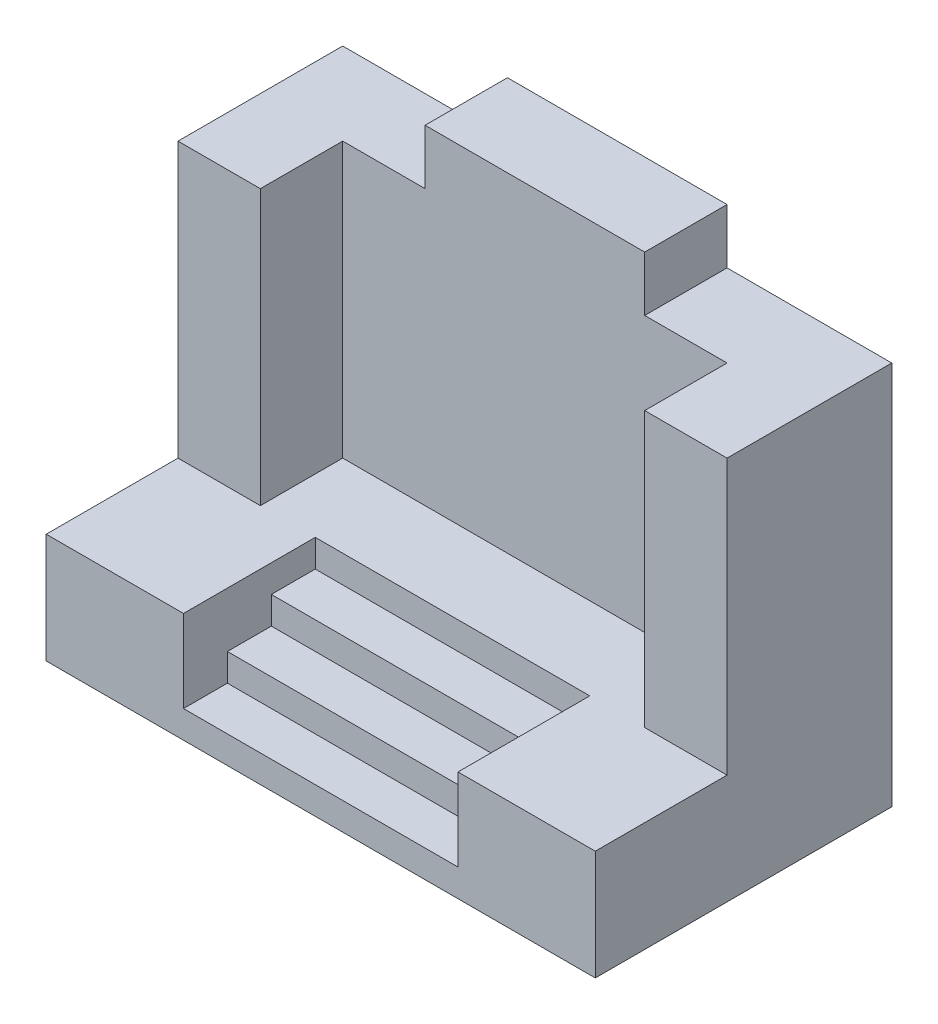
SolidWorks part; units mm, degrees
ref_plane "Front Plane" through (0, 0, 0) normal (0, 0, 1) x (1, 0, 0)
ref_plane "Top Plane" through (0, 0, 0) normal (0, 1, 0) x (1, 0, 0)
ref_plane "Right Plane" through (0, 0, 0) normal (1, 0, 0) x (0, 0, -1)
sketch "Sketch1" plane through (0, 0, 0) normal (0, 1, 0) x (1, 0, 0)
  line L0 (0, 82.5623) -> (0, -99.9459) construction
  line L1 (-500, 0) -> (500, 0)
  line L2 (-500, 0) -> (-500, 540)
  line L3 (-500, 540) -> (500, 540)
  line L4 (500, 0) -> (500, 540)
  line L5 (-250, 0) -> (250, 0)
  line L6 (-250, 0) -> (-250, 240)
  line L7 (-250, 240) -> (250, 240)
  line L8 (250, 0) -> (250, 240)
  line L9 (-500, 240) -> (-350, 240)
  line L10 (-350, 240) -> (-350, 390)
  line L11 (-350, 390) -> (350, 390)
  line L12 (350, 390) -> (350, 240)
  line L13 (350, 240) -> (500, 240)
  line L14 (-250, 80) -> (250, 80)
  line L15 (-250, 160) -> (250, 160)
  line L16 (200, 540) -> (200, 390)
  line L17 (-200, 390) -> (-200, 540)
  dimension "D1" = 1000
  dimension "D2" = 500
  dimension "D3" = 80
  dimension "D4" = 80
  dimension "D5" = 80
  dimension "D6" = 150
  dimension "D7" = 700
  dimension "D8" = 300
  dimension "D9" = 540
  dimension "D10" = 300
extrude "Boss-Extrude1" add sketch "Sketch1" along normal blind 700 contours L3 L16 L11 L12 L13 L4 | L11 L17 L3 L2 L9 L10 region at (-375, 0, -415) region at (375, 0, -415)
extrude "Boss-Extrude2" add sketch "Sketch1<3>" along normal blind 200 contours L13 L12 L11 L10 L9 L2 L1 L6 L7 L8 L4 region at (-489.2664, 0, -120)
sketch "Sketch1<3>" plane through (0, 0, 0) normal (0, 1, 0) x (1, 0, 0) same geometry as "Sketch1"
extrude "Boss-Extrude3" add sketch "Sketch1<4>" along normal blind 800 contours L17 L11 L16 L3 region at (0, 0, -465)
sketch "Sketch1<4>" plane through (0, 0, 0) normal (0, 1, 0) x (1, 0, 0) same geometry as "Sketch1"
extrude "Boss-Extrude4" add sketch "Sketch1<5>" along normal blind 150 contours L6 L15 L8 L7 region at (0, 0, -200)
sketch "Sketch1<5>" plane through (0, 0, 0) normal (0, 1, 0) x (1, 0, 0) same geometry as "Sketch1"
extrude "Boss-Extrude5" add sketch "Sketch1<6>" along normal blind 100 contours L15 L6 L14 L8 region at (0, 0, -120)
sketch "Sketch1<6>" plane through (0, 0, 0) normal (0, 1, 0) x (1, 0, 0) same geometry as "Sketch1"
extrude "Boss-Extrude6" add sketch "Sketch1<7>" along normal blind 50 contours L14 L0 L5 L8 | L0 L14 L6 L1 region at (125, 0, -40) region at (-125, 0, -40)
sketch "Sketch1<7>" plane through (0, 0, 0) normal (0, 1, 0) x (1, 0, 0) same geometry as "Sketch1"
